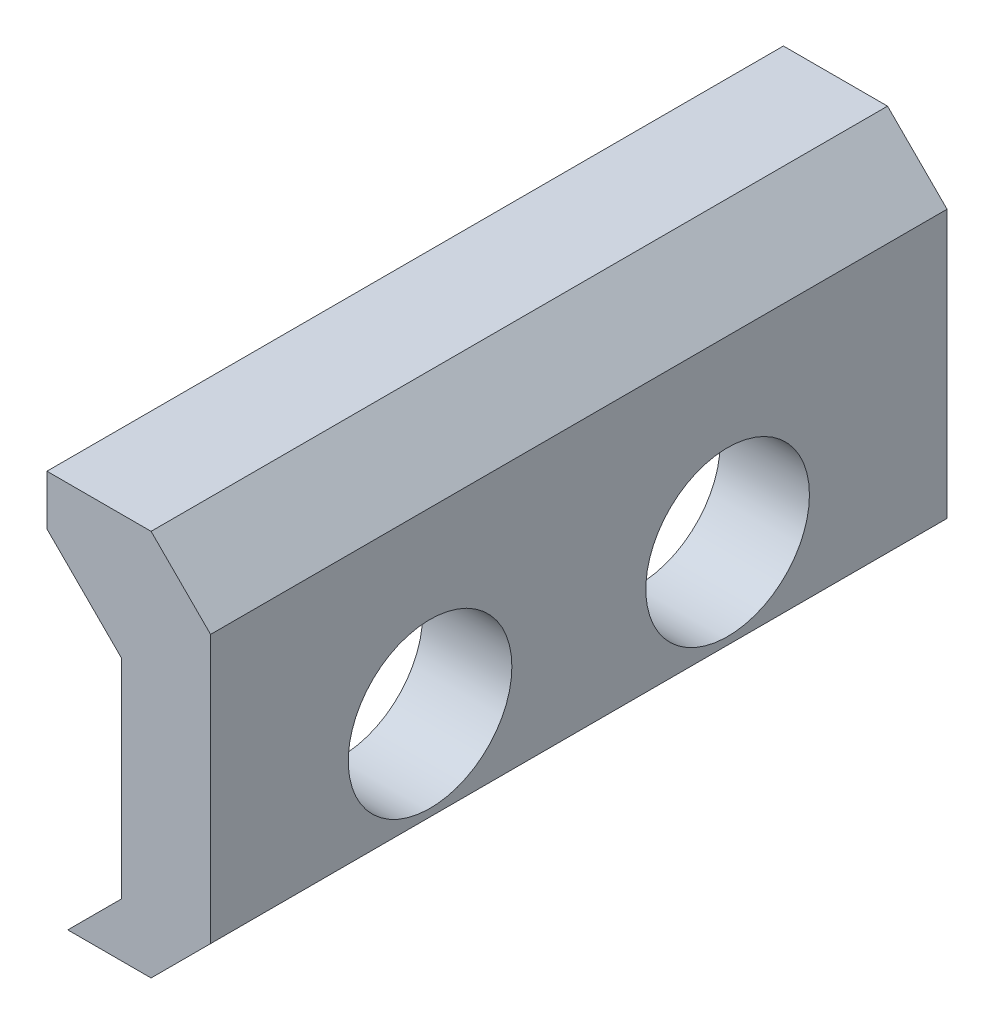
SolidWorks part; units mm, degrees
ref_plane "Płaszczyzna przednia" through (0, 0, 0) normal (0, 0, 1) x (1, 0, 0)
ref_plane "Płaszczyzna górna" through (0, 0, 0) normal (0, 1, 0) x (1, 0, 0)
ref_plane "Płaszczyzna prawa" through (0, 0, 0) normal (1, 0, 0) x (0, 0, -1)
sketch "Szkic1" plane through (0, 0, 0) normal (0, 0, 1) x (1, 0, 0)
  line L0 (3, -8.82) -> (-1.8, -8.82)
  line L4 (3, -8.82) -> (3, 4.18)
  line L5 (0, 0) -> (-3.13, -3.13) construction
  line L7 (-1.8, -8.82) -> (0, -7.02)
  line L8 (0, -7.02) -> (0, 0)
  line L9 (0, 0) -> (-2.5, 2.5)
  line L10 (-2.5, 2.5) -> (-2.5, 4.18)
  line L11 (-2.5, 4.18) -> (3, 4.18)
  line L13 (-1.37, 1.37) -> (-6.4624, 1.37) construction
  line L14 (-1.37, 1.37) -> (-1.37, -1.37) construction
  line L15 (-1.37, -1.37) -> (-6.4624, -1.37) construction
  line L16 (-6.4624, 1.37) -> (-6.4624, -1.37) construction
  dimension "D1" = 13
  dimension "D2" = 45
  dimension "D3" = 1.68
  dimension "D4" = 5.5
  dimension "D5" = 2.74
  dimension "D6" = 4.5
  dimension "D7" = 45
  dimension "D8" = 3
  dimension "D9" = 1.8
extrude "Dodanie-wyciągnięcie1" add sketch "Szkic1" along normal blind 24.75
sketch "Szkic2" plane through (3, 0, 0) normal (1, 0, 0) x (0, 0, -1)
  line L0 (-24.75, -8.82) -> (0, -8.82) construction
  line L1 (-24.75, 4.18) -> (0, 4.18) construction
  circle A0 centre (-17.375, -3.82) radius 2.75
  circle A1 centre (-7.375, -3.82) radius 2.75
  circle A2 centre (-17.375, -3.82) radius 2.15 construction
  circle A3 centre (-7.375, -3.82) radius 2.15 construction
  dimension "D1" = 13
extrude "Wytnij-wyciągnięcie1" cut sketch "Szkic2" against normal blind 4.2
chamfer "Chamfer1" distance 2 angle 45 2 edges at (3, -8.82, 12.375) (3, 4.18, 12.375)
